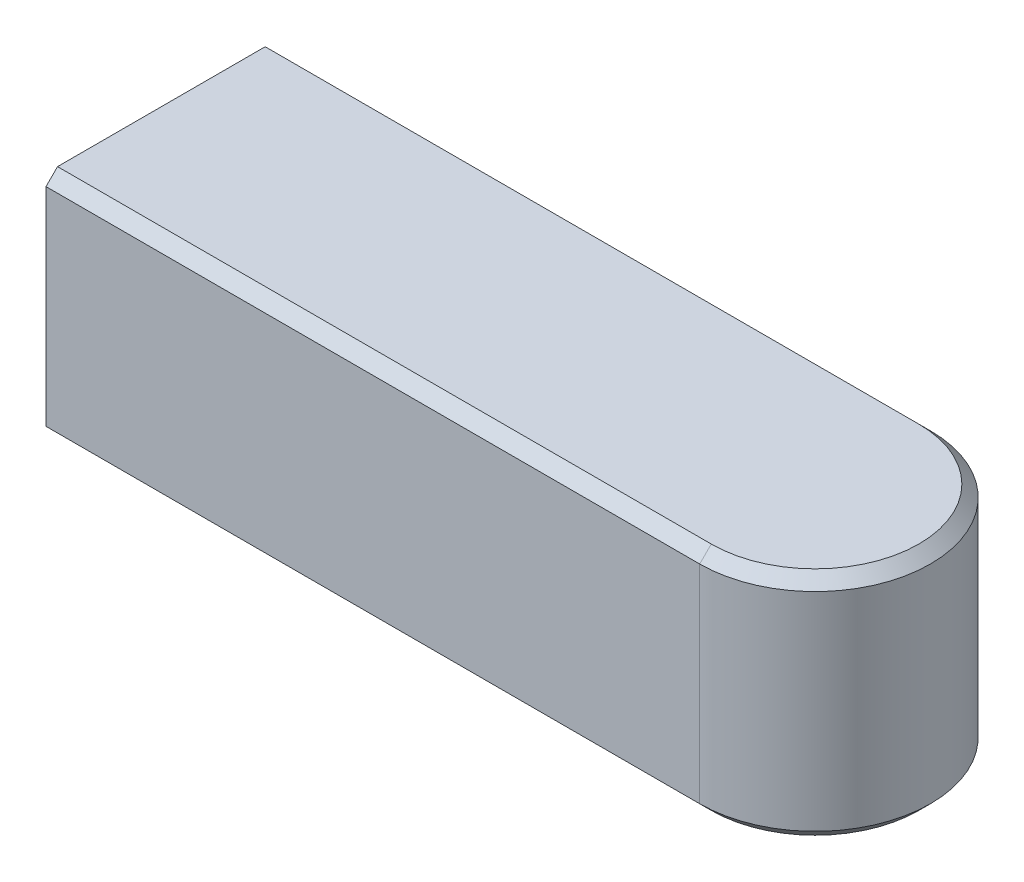
SolidWorks part; units mm, degrees
material "S45C"
ref_plane "Front Plane" through (0, 0, 0) normal (0, 0, 1) x (1, 0, 0)
ref_plane "Top Plane" through (0, 0, 0) normal (0, 1, 0) x (1, 0, 0)
ref_plane "Right Plane" through (0, 0, 0) normal (1, 0, 0) x (0, 0, -1)
sketch "Sketch1" plane through (0, 0, 0) normal (0, 1, 0) x (1, 0, 0)
  line L0 (-10, 0) -> (10, 0) construction
  line L1 (0, 3) -> (0, -3) construction
  line L3 (-10, 3) -> (10, 3)
  line L4 (-10, 3) -> (-10, -3)
  line L5 (-10, -3) -> (10, -3)
  line L6 (10, 3) -> (10, -3)
  dimension "L" = 20
  dimension "B" = 6
extrude "Boss-Extrude1" add sketch "Sketch1" along normal blind 6
chamfer "Chamfer1" [suppressed] distance 0.3 angle 45
fillet "Fillet1" [suppressed] type full round
fillet "Fillet2" 2 edges at (10, 3, 3) (10, 3, -3) type full round first side face at (0, 3, 3) second side face at (0, 3, -3) middle face at (10, 3, 0)
chamfer "Chamfer2" distance 0.3 angle 45 6 edges at (-1.5, 0, -3) (10, 0, 0) (-1.5, 0, 3) (-1.5, 6, -3) (10, 6, 0) (-1.5, 6, 3)
